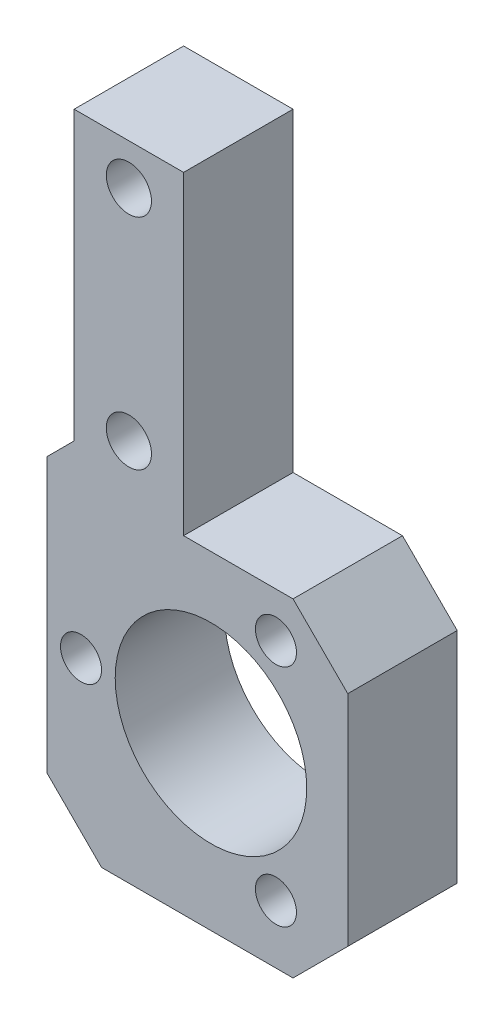
SolidWorks part; units mm, degrees
ref_plane "Front" through (0, 0, 0) normal (0, 0, 1) x (1, 0, 0)
ref_plane "Top" through (0, 0, 0) normal (0, 1, 0) x (1, 0, 0)
ref_plane "Right" through (0, 0, 0) normal (1, 0, 0) x (0, 0, -1)
sketch "Esquisse1" plane through (0, 0, 0) normal (0, 0, 1) x (1, 0, 0)
  line L0 (0, 12.5) -> (22, 12.5) construction
  line L1 (0, 0) -> (22, 0)
  line L2 (0, 0) -> (0, 24)
  line L3 (0, 24) -> (22, 24)
  line L4 (22, 0) -> (22, 24)
  line L5 (12, 12.5) -> (12, 19.5) construction
  line L6 (12, 12.5) -> (2.5, 12.5) construction
  line L7 (12, 12.5) -> (16.75, 20.7272) construction
  circle A0 centre (12, 12.5) radius 7
  circle A1 centre (2.5, 12.5) radius 1.5
  circle A2 centre (16.75, 20.7272) radius 1.5
  circle A3 centre (16.75, 4.2728) radius 1.5
  dimension "D3" = 14
  dimension "D5" = 3
  dimension "D6" = 9.5
  dimension "D1" = 22
  dimension "D2" = 24
  dimension "D4" = 12.5
  dimension "D8" = 120
  dimension "D9" = 12
  dimension "D7" = 3
extrude "Boss.-Extru.1" add sketch "Esquisse1" along normal blind 8
sketch "Esquisse2" plane through (0, 0, 8) normal (0, 0, 1) x (1, 0, 0)
  line L0 (22, 24) -> (0, 24) construction
  line L1 (10, 24) -> (2, 24)
  line L2 (10, 24) -> (10, 47)
  line L3 (10, 47) -> (2, 47)
  line L4 (2, 24) -> (2, 47)
  line L5 (0, 24) -> (0, 0) construction
  dimension "D1" = 23
  dimension "D2" = 8
  dimension "D3" = 2
extrude "Boss.-Extru.2" add sketch "Esquisse2" against normal up to vertex (8 mm away) up to point (22, 24, 0)
sketch "Esquisse4" plane through (0, 0, 8) normal (0, 0, 1) x (1, 0, 0)
  line L0 (6, 47) -> (6, 28) construction
  line L1 (10, 47) -> (2, 47) construction
  line L2 (2, 24) -> (0, 24) construction
  circle A0 centre (6, 28) radius 1.65
  circle A1 centre (6, 44) radius 1.65
  dimension "D1" = 3.3
  dimension "D2" = 16
  dimension "D3" = 4
extrude "Enlèv. mat.-Extru.1" cut sketch "Esquisse4" against normal through all
chamfer "Chanfrein1" distance 4 angle 45 3 edges at (22, 24, 4) (22, 0, 4) (0, 0, 4)
chamfer "Chanfrein2" distance 2 angle 45 1 edges at (2, 24, 4)
